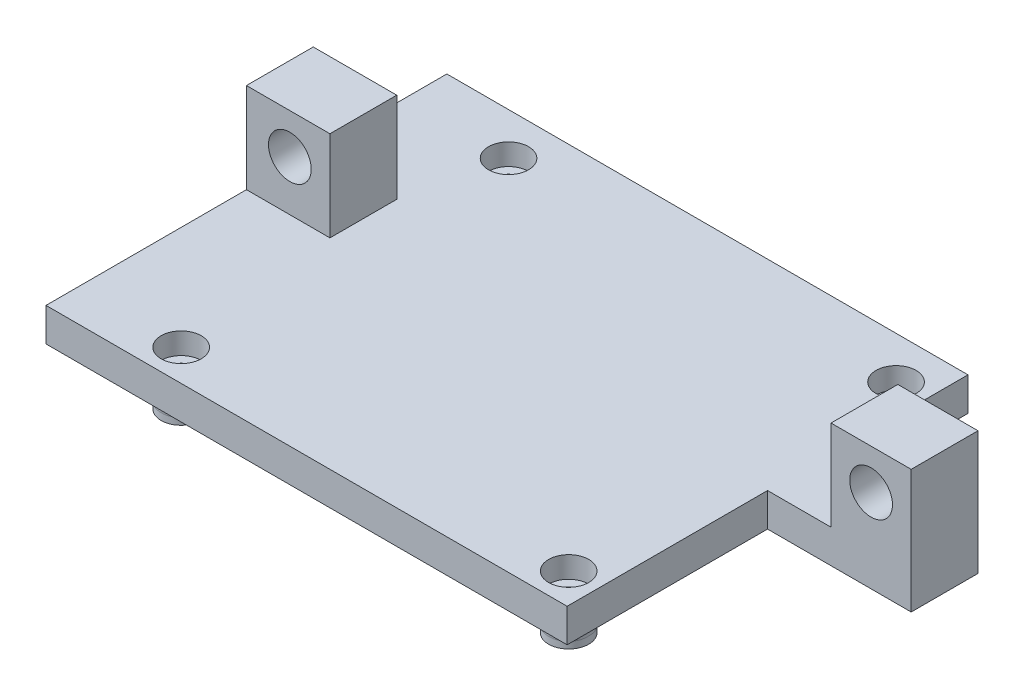
SolidWorks part; units mm, degrees
ref_plane "Front Plane" through (0, 0, 0) normal (0, 0, 1) x (1, 0, 0)
ref_plane "Top Plane" through (0, 0, 0) normal (0, 1, 0) x (1, 0, 0)
ref_plane "Right Plane" through (0, 0, 0) normal (1, 0, 0) x (0, 0, -1)
sketch "Sketch1" plane through (0, 0, 0) normal (0, 0, 1) x (1, 0, 0)
  line L0 (99.5, 3.2071) -> (99.5, 69.7929) construction
  line L1 (99.5, 12.5) -> (87.5, 12.5)
  line L2 (99.5, 12.5) -> (99.5, -6)
  line L3 (99.5, -6) -> (0, -6)
  line L4 (0, 12.5) -> (0, -6)
  line L5 (12.5, 12.5) -> (0, 12.5)
  line L7 (87.5, 12.5) -> (87.5, -1)
  line L8 (87.5, -1) -> (12.5, -1)
  line L9 (12.5, 12.5) -> (12.5, -1)
  line L12 (53.5, 0) -> (97, 0) construction
  line L13 (0, 70) -> (0, 3) construction
  line L14 (87.5, 30.5) -> (87.5, 0.5) construction
  line L15 (12.5, 0.5) -> (12.5, 30.5) construction
  circle A0 centre (93.5, 6.5) radius 3.2
  circle A1 centre (6.5, 6.5) radius 3.2
  point P24 (50, -1)
  dimension "D1" = 6.4
  dimension "D2" = 6.4
  dimension "D3" = 1
  dimension "D4" = 6
  dimension "D5" = 5
extrude "Boss-Extrude1" add sketch "Sketch1" along normal blind 10
sketch "Sketch2" plane through (0, 0, 10) normal (0, 0, 1) x (1, 0, 0)
  line L0 (0, 12.5) -> (0, -6) construction
  line L1 (0, -6) -> (78, -6)
  line L2 (0, -6) -> (0, -1)
  line L3 (0, -1) -> (78, -1)
  line L4 (78, -6) -> (78, -1)
  line L7 (87.5, -1) -> (12.5, -1) construction
  dimension "D1" = 78
  dimension "D4" = 5
extrude "Boss-Extrude2" add sketch "Sketch2" along normal mid plane 60
sketch "Sketch3" plane through (0, -6, 0) normal (0, -1, 0) x (1, 0, 0)
  line L0 (44.544, -40.0805) -> (44.544, 104.2476) construction
  circle A0 centre (15.544, 35.31) radius 1.6
  circle A1 centre (73.544, 35.31) radius 1.6
  circle A2 centre (15.544, -13.69) radius 1.6
  circle A3 centre (73.544, -13.69) radius 1.6
  arc A4 (14.194, -13.69) -> (16.894, -13.69) centre (15.544, -13.69) ccw construction
  dimension "D4" = 3.2
  dimension "D5" = 3.2
  dimension "D6" = 3.2
  dimension "D7" = 3.2
  dimension "D1" = 49
  dimension "D2" = 58
  dimension "D3" = 29
sketch "Sketch4" plane through (0, -6, 0) normal (0, -1, 0) x (1, 0, 0)
  circle A0 centre (15.544, 35.31) radius 3
  circle A1 centre (73.544, 35.31) radius 3
  circle A2 centre (73.544, -13.69) radius 3
  circle A3 centre (15.544, -13.69) radius 3
  arc A4 (14.194, -13.69) -> (16.894, -13.69) centre (15.544, -13.69) ccw construction
  arc A5 (14.194, 35.31) -> (16.894, 35.31) centre (15.544, 35.31) ccw construction
  arc A6 (72.194, 35.31) -> (74.894, 35.31) centre (73.544, 35.31) ccw construction
  arc A7 (72.244, -13.69) -> (74.844, -13.69) centre (73.544, -13.69) ccw construction
  dimension "D1" = 6
  dimension "D2" = 6
  dimension "D3" = 6
  dimension "D4" = 6
extrude "Boss-Extrude3" add sketch "Sketch4" along normal blind 3
extrude "Cut-Extrude1" cut sketch "Sketch4<2>" against normal up to next from offset 1.8 offset against normal yes
sketch "Sketch4<2>" plane through (0, -6, 0) normal (0, -1, 0) x (1, 0, 0) same geometry as "Sketch4"
extrude "Cut-Extrude2" cut sketch "Sketch3" against normal through all both and the other way through all
fillet "Fillet1" radius 2 4 edges at (70.544, -6, -13.69) (12.544, -6, -13.69) (70.544, -6, 35.31) (12.544, -6, 35.31)
